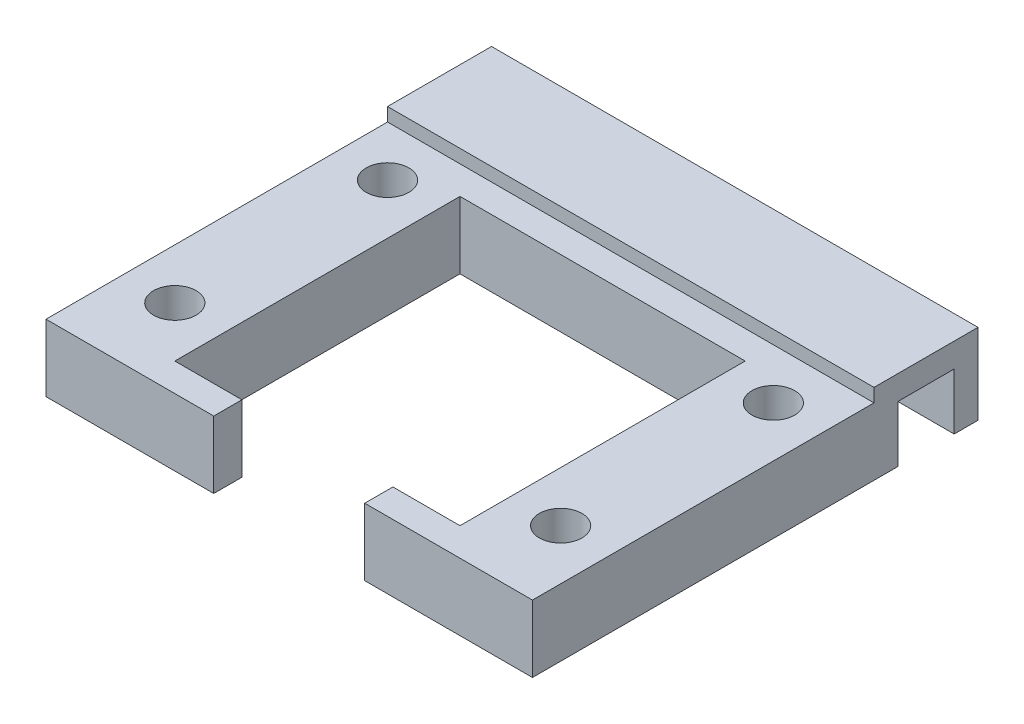
SolidWorks part; units mm, degrees
ref_plane "Front Plane" through (0, 0, 0) normal (0, 0, 1) x (1, 0, 0)
ref_plane "Top Plane" through (0, 0, 0) normal (0, 1, 0) x (1, 0, 0)
ref_plane "Right Plane" through (0, 0, 0) normal (1, 0, 0) x (0, 0, -1)
sketch "Sketch1" plane through (0, 0, 0) normal (0, 1, 0) x (1, 0, 0)
  line L1 (0, 0) -> (42.5, 0)
  line L2 (0, 0) -> (0, 42.5)
  line L3 (0, 42.5) -> (42.5, 42.5)
  line L4 (42.5, 0) -> (42.5, 42.5)
  line L5 (-15, 0) -> (57.5, 0)
  line L6 (-15, 0) -> (-15, 46.7)
  line L7 (-15, 46.7) -> (57.5, 46.7)
  line L8 (57.5, 0) -> (57.5, 46.7)
  line L9 (-15, 0) -> (10, 0)
  line L10 (-15, 0) -> (-15, -4.2)
  line L11 (-15, -4.2) -> (10, -4.2)
  line L12 (10, 0) -> (10, -4.2)
  line L13 (57.5, 0) -> (32.5, 0)
  line L14 (57.5, 0) -> (57.5, -4.2)
  line L15 (57.5, -4.2) -> (32.5, -4.2)
  line L16 (32.5, 0) -> (32.5, -4.2)
  circle A0 centre (-7.5, 7.5) radius 3.175
  circle A1 centre (-7.5, 39.2) radius 3.175
  circle A2 centre (50, 39.2) radius 3.175
  circle A3 centre (50, 7.5) radius 3.175
  dimension "D5" = 6.35
  dimension "D1" = 42.5
  dimension "D2" = 15
  dimension "D3" = 15
  dimension "D4" = 4.2
  dimension "D6" = 7.5
  dimension "D7" = 7.5
  dimension "D8" = 7.5
  dimension "D9" = 7.5
  dimension "D10" = 4.2
  dimension "D11" = 10
extrude "Boss-Extrude1" add sketch "Sketch1" along normal blind 10 contours L5 L8 L7 L6 L2 L3 L4 A3 A2 A1 A0 | L12 L1 L5 L10 L11 | L1 L16 L15 L14 L5 region at (-7.5, 0, -0.8624) region at (-2.5, 0, 2.1) region at (45, 0, 2.1)
sketch "Sketch4" plane through (57.5, 0, 0) normal (1, 0, 0) x (0, 0, -1)
  line L0 (58.65, 8.4) -> (62.2, 8.4) construction
  line L1 (46.7, 0) -> (62.2, 0)
  line L2 (46.7, 0) -> (46.7, 12)
  line L3 (46.7, 12) -> (62.2, 12)
  line L4 (62.2, 0) -> (62.2, 12)
  line L5 (50.25, 0) -> (58.65, 0)
  line L6 (50.25, 0) -> (50.25, 8.4)
  line L7 (50.25, 8.4) -> (58.65, 8.4)
  line L8 (58.65, 0) -> (58.65, 8.4)
  line L9 (50.25, 8.4) -> (46.7, 8.4) construction
  line M12 (46.7, 0) -> (46.7, 10)
  dimension "D1" = 15.5
  dimension "D2" = 12
  dimension "D3" = 8.4
extrude "Boss-Extrude3" add sketch "Sketch4" against normal up to surface (72.5 mm away) contours L8 L1 L4 L3 L2 L6 L7 M12 region at (57.5, 5, -46.896) up to face at (-15, 5, -21.25)
equation "\"8mm hole\" = 8.4mm"
equation "\"22mm hole\"= 23mm"
equation "\"15mm hole\"= 15.8mm"
equation "\"bed height offset\"= 3mm"
equation "\"motor width\"= 42.5mm"
equation "\"D3@Sketch4\"= \"8mm hole\""
